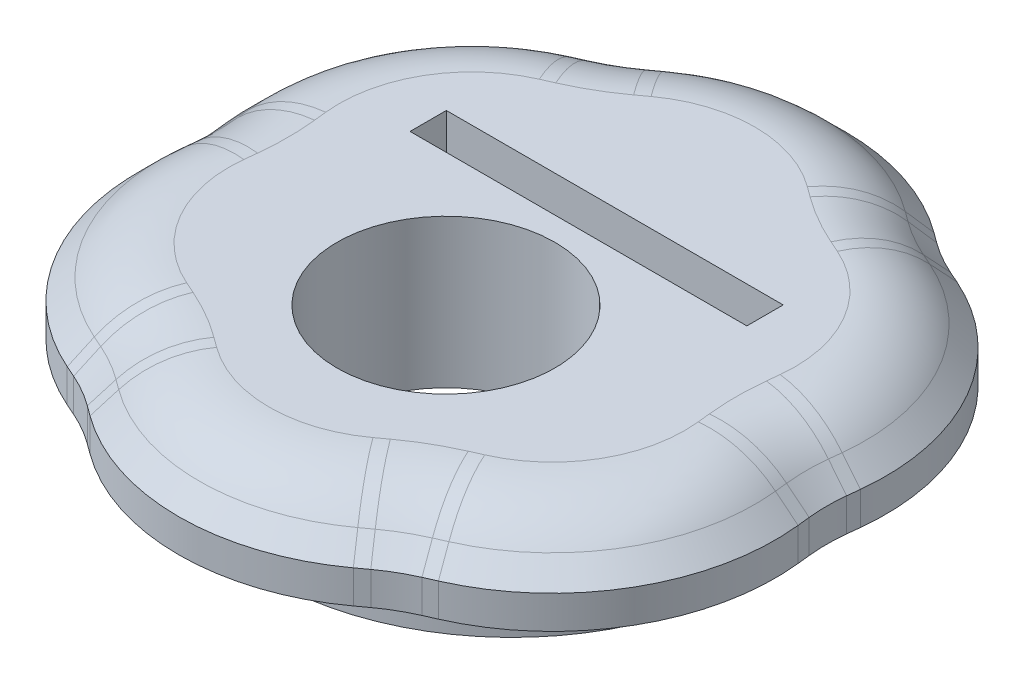
SolidWorks part; units mm, degrees
ref_plane "前基準面" through (0, 0, 0) normal (0, 0, 1) x (1, 0, 0)
ref_plane "上基準面" through (0, 0, 0) normal (0, 1, 0) x (1, 0, 0)
ref_plane "右基準面" through (0, 0, 0) normal (1, 0, 0) x (0, 0, -1)
sketch "草圖1" plane through (0, 0, 0) normal (0, 1, 0) x (1, 0, 0)
  line L14 (-20.705, 1.7245) -> (-20.6232, 0.9719)
  line L19 (-20.6232, -0.9719) -> (-20.705, -1.7245)
  line L20 (-11.846, -17.0688) -> (-11.1533, -17.3743)
  line L21 (-9.4699, -18.3462) -> (-8.859, -18.7933)
  line L22 (8.859, -18.7933) -> (9.4699, -18.3462)
  line L23 (11.1533, -17.3743) -> (11.846, -17.0688)
  line L24 (20.705, -1.7245) -> (20.6232, -0.9719)
  line L25 (20.6232, 0.9719) -> (20.705, 1.7245)
  line L26 (11.846, 17.0688) -> (11.1533, 17.3743)
  line L27 (9.4699, 18.3462) -> (8.859, 18.7933)
  line L28 (-8.859, 18.7933) -> (-9.4699, 18.3462)
  line L29 (-11.1533, 17.3743) -> (-11.846, 17.0688)
  arc A13 (-11.846, 17.0688) -> (-20.705, 1.7245) centre (-5.7927, 3.3444) ccw
  arc A14 (-20.6232, 0.9719) -> (-20.6232, -0.9719) centre (-29.5706, 0) cw
  arc A15 (-20.705, -1.7245) -> (-11.846, -17.0688) centre (-5.7927, -3.3444) ccw
  arc A16 (-9.4699, -18.3462) -> (-11.1533, -17.3743) centre (-14.7853, -25.6089) ccw
  arc A17 (-8.859, -18.7933) -> (8.859, -18.7933) centre (0, -6.6888) ccw
  arc A18 (11.1533, -17.3743) -> (9.4699, -18.3462) centre (14.7853, -25.6089) ccw
  arc A19 (11.846, -17.0688) -> (20.705, -1.7245) centre (5.7927, -3.3444) ccw
  arc A20 (20.6232, 0.9719) -> (20.6232, -0.9719) centre (29.5706, 0) ccw
  arc A21 (20.705, 1.7245) -> (11.846, 17.0688) centre (5.7927, 3.3444) ccw
  arc A22 (9.4699, 18.3462) -> (11.1533, 17.3743) centre (14.7853, 25.6089) ccw
  arc A23 (8.859, 18.7933) -> (-8.859, 18.7933) centre (0, 6.6888) ccw
  arc A24 (-11.1533, 17.3743) -> (-9.4699, 18.3462) centre (-14.7853, 25.6089) ccw
  point P20 (0, 0)
extrude "填料-伸長1" add sketch "草圖1" along normal blind 3
chamfer "導角1" distance 4.5 angle 45 24 edges at (0, 3, -21.6888) (-9.1645, 3, -18.5698) (9.1645, 3, -18.5698) (-10.2853, 3, -17.8147) (10.2853, 3, -17.8147) (-11.4997, 3, -17.2215) (11.4997, 3, -17.2215) (-18.7831, 3, -10.8444) (18.7831, 3, -10.8444) (-20.6641, 3, -1.3482) (20.6641, 3, -1.3482) (-20.5706, 3, 0) (20.5706, 3, 0) (-20.6641, 3, 1.3482) (20.6641, 3, 1.3482) (-18.7831, 3, 10.8444) (18.7831, 3, 10.8444) (-11.4997, 3, 17.2215) (11.4997, 3, 17.2215) (-10.2853, 3, 17.8147) (10.2853, 3, 17.8147) (-9.1645, 3, 18.5698) (9.1645, 3, 18.5698) (0, 3, 21.6888)
sketch "草圖3" plane through (0, 0, 0) normal (0, -1, 0) x (1, 0, 0)
  circle A0 centre (0, 0) radius 14.75
  circle A1 centre (0, 0) radius 14
  dimension "D1" = 29.5
  dimension "D2" = 28
extrude "填料-伸長2" add sketch "草圖3" along normal blind 6
fillet "圓角1" radius 6 24 edges at (-6.5067, 3, 14.9384) (-8.0353, 3, 13.9175) (-9.6837, 3, 13.1042) (-14.886, 3, 8.5944) (-16.1904, 3, 1.8342) (-16.0706, 3, 0) (-16.1904, 3, -1.8342) (-14.886, 3, -8.5944) (-9.6837, 3, -13.1042) (-8.0353, 3, -13.9175) (-6.5067, 3, -14.9384) (0, 3, -17.1888) (6.5067, 3, -14.9384) (8.0353, 3, -13.9175) (9.6837, 3, -13.1042) (14.886, 3, -8.5944) (16.1904, 3, -1.8342) (16.0706, 3, 0) (16.1904, 3, 1.8342) (14.886, 3, 8.5944) (9.6837, 3, 13.1042) (8.0353, 3, 13.9175) (6.5067, 3, 14.9384) (0, 3, 17.1888)
sketch "草圖4" plane through (0, 3, 0) normal (0, 1, 0) x (1, 0, 0)
  line L1 (-10.2, 6.224) -> (10.2, 6.224)
  line L2 (-10.2, 6.224) -> (-10.2, 4.024)
  line L3 (-10.2, 4.024) -> (10.2, 4.024)
  line L4 (10.2, 6.224) -> (10.2, 4.024)
  circle A0 centre (0, -4) radius 6.6
  dimension "D1" = 4
  dimension "D5" = 13.2
  dimension "D2" = 20.4
  dimension "D3" = 10.2
  dimension "D4" = 2.2
extrude "除料-伸長1" cut sketch "草圖4" against normal blind 10
sketch "草圖5" plane through (0, 0, 0) normal (0, -1, 0) x (1, 0, 0)
  circle A0 centre (0, 4) radius 6.6
  circle A1 centre (0, 4) radius 7.5
  dimension "D1" = 15
extrude "填料-伸長3" add sketch "草圖5" along normal blind 6
sketch "草圖6" plane through (0, 0, 0) normal (0, -1, 0) x (1, 0, 0)
  line L12 (-7.9934, -16.3288) -> (-7.3825, -16.7759)
  line L13 (7.3825, -16.7759) -> (7.9934, -16.3288)
  line L14 (10.1445, -15.0869) -> (10.8371, -14.7814)
  line L15 (18.2196, -1.9945) -> (18.1379, -1.2419)
  line L16 (18.1379, 1.2419) -> (18.2196, 1.9945)
  line L17 (10.8371, 14.7814) -> (10.1445, 15.0869)
  line L18 (7.9934, 16.3288) -> (7.3825, 16.7759)
  line L19 (-7.3825, 16.7759) -> (-7.9934, 16.3288)
  line L20 (-10.1445, 15.0869) -> (-10.8371, 14.7814)
  line L21 (-18.2196, 1.9945) -> (-18.1379, 1.2419)
  line L22 (-18.1379, -1.2419) -> (-18.2196, -1.9945)
  line L23 (-10.8371, -14.7814) -> (-10.1445, -15.0869)
  line L24 (-8.584, -17.1358) -> (-7.9731, -17.5829)
  line L25 (7.9731, -17.5829) -> (8.584, -17.1358)
  line L26 (10.548, -16.0018) -> (11.2406, -15.6963)
  line L27 (19.2138, -1.8865) -> (19.132, -1.1339)
  line L28 (19.132, 1.1339) -> (19.2138, 1.8865)
  line L29 (11.2406, 15.6963) -> (10.548, 16.0018)
  line L30 (8.584, 17.1358) -> (7.9731, 17.5829)
  line L31 (-7.9731, 17.5829) -> (-8.584, 17.1358)
  line L32 (-10.548, 16.0018) -> (-11.2406, 15.6963)
  line L33 (-19.2138, 1.8865) -> (-19.132, 1.1339)
  line L34 (-19.132, -1.1339) -> (-19.2138, -1.8865)
  line L35 (-11.2406, -15.6963) -> (-10.548, -16.0018)
  line L36 (-8.584, -17.1358) -> (-7.9731, -17.5829)
  line L37 (7.9731, -17.5829) -> (8.584, -17.1358)
  line L38 (10.548, -16.0018) -> (11.2406, -15.6963)
  line L39 (19.2138, -1.8865) -> (19.132, -1.1339)
  line L40 (19.132, 1.1339) -> (19.2138, 1.8865)
  line L41 (11.2406, 15.6963) -> (10.548, 16.0018)
  line L42 (8.584, 17.1358) -> (7.9731, 17.5829)
  line L43 (-7.9731, 17.5829) -> (-8.584, 17.1358)
  line L44 (-10.548, 16.0018) -> (-11.2406, 15.6963)
  line L45 (-19.2138, 1.8865) -> (-19.132, 1.1339)
  line L46 (-19.132, -1.1339) -> (-19.2138, -1.8865)
  line L47 (-11.2406, -15.6963) -> (-10.548, -16.0018)
  arc A12 (-7.3825, -16.7759) -> (7.3825, -16.7759) centre (0, -6.6888) ccw
  arc A13 (10.1445, -15.0869) -> (7.9934, -16.3288) centre (14.7853, -25.6089) ccw
  arc A14 (10.8371, -14.7814) -> (18.2196, -1.9945) centre (5.7927, -3.3444) ccw
  arc A15 (18.1379, 1.2419) -> (18.1379, -1.2419) centre (29.5706, 0) ccw
  arc A16 (18.2196, 1.9945) -> (10.8371, 14.7814) centre (5.7927, 3.3444) ccw
  arc A17 (7.9934, 16.3288) -> (10.1445, 15.0869) centre (14.7853, 25.6089) ccw
  arc A18 (7.3825, 16.7759) -> (-7.3825, 16.7759) centre (0, 6.6888) ccw
  arc A19 (-10.1445, 15.0869) -> (-7.9934, 16.3288) centre (-14.7853, 25.6089) ccw
  arc A20 (-10.8371, 14.7814) -> (-18.2196, 1.9945) centre (-5.7927, 3.3444) ccw
  arc A21 (-18.1379, -1.2419) -> (-18.1379, 1.2419) centre (-29.5706, 0) ccw
  arc A22 (-18.2196, -1.9945) -> (-10.8371, -14.7814) centre (-5.7927, -3.3444) ccw
  arc A23 (-7.9934, -16.3288) -> (-10.1445, -15.0869) centre (-14.7853, -25.6089) ccw
  arc A24 (-7.9731, -17.5829) -> (7.9731, -17.5829) centre (0, -6.6888) ccw
  arc A25 (10.548, -16.0018) -> (8.584, -17.1358) centre (14.7853, -25.6089) ccw
  arc A26 (11.2406, -15.6963) -> (19.2138, -1.8865) centre (5.7927, -3.3444) ccw
  arc A27 (19.132, 1.1339) -> (19.132, -1.1339) centre (29.5706, 0) ccw
  arc A28 (19.2138, 1.8865) -> (11.2406, 15.6963) centre (5.7927, 3.3444) ccw
  arc A29 (8.584, 17.1358) -> (10.548, 16.0018) centre (14.7853, 25.6089) ccw
  arc A30 (7.9731, 17.5829) -> (-7.9731, 17.5829) centre (0, 6.6888) ccw
  arc A31 (-10.548, 16.0018) -> (-8.584, 17.1358) centre (-14.7853, 25.6089) ccw
  arc A32 (-11.2406, 15.6963) -> (-19.2138, 1.8865) centre (-5.7927, 3.3444) ccw
  arc A33 (-19.132, -1.1339) -> (-19.132, 1.1339) centre (-29.5706, 0) ccw
  arc A34 (-19.2138, -1.8865) -> (-11.2406, -15.6963) centre (-5.7927, -3.3444) ccw
  arc A35 (-8.584, -17.1358) -> (-10.548, -16.0018) centre (-14.7853, -25.6089) ccw
  arc A36 (-7.9731, -17.5829) -> (7.9731, -17.5829) centre (0, -6.6888) ccw
  arc A37 (10.548, -16.0018) -> (8.584, -17.1358) centre (14.7853, -25.6089) ccw
  arc A38 (11.2406, -15.6963) -> (19.2138, -1.8865) centre (5.7927, -3.3444) ccw
  arc A39 (19.132, 1.1339) -> (19.132, -1.1339) centre (29.5706, 0) ccw
  arc A40 (19.2138, 1.8865) -> (11.2406, 15.6963) centre (5.7927, 3.3444) ccw
  arc A41 (8.584, 17.1358) -> (10.548, 16.0018) centre (14.7853, 25.6089) ccw
  arc A42 (7.9731, 17.5829) -> (-7.9731, 17.5829) centre (0, 6.6888) ccw
  arc A43 (-10.548, 16.0018) -> (-8.584, 17.1358) centre (-14.7853, 25.6089) ccw
  arc A44 (-11.2406, 15.6963) -> (-19.2138, 1.8865) centre (-5.7927, 3.3444) ccw
  arc A45 (-19.132, -1.1339) -> (-19.132, 1.1339) centre (-29.5706, 0) ccw
  arc A46 (-19.2138, -1.8865) -> (-11.2406, -15.6963) centre (-5.7927, -3.3444) ccw
  arc A47 (-8.584, -17.1358) -> (-10.548, -16.0018) centre (-14.7853, -25.6089) ccw
  dimension "D1" = 0
  dimension "D2" = 1
extrude "填料-伸長4" add sketch "草圖6" along normal blind 2
